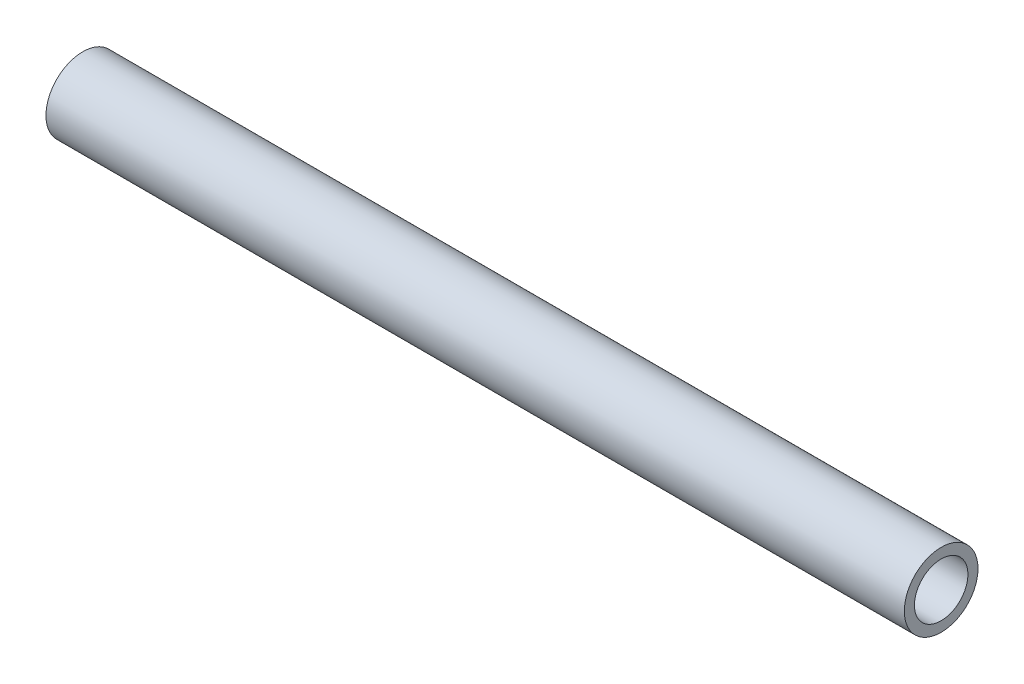
SolidWorks part; units mm, degrees
ref_plane "Front Plane" through (0, 0, 0) normal (0, 0, 1) x (1, 0, 0)
ref_plane "Top Plane" through (0, 0, 0) normal (0, 1, 0) x (1, 0, 0)
ref_plane "Right Plane" through (0, 0, 0) normal (1, 0, 0) x (0, 0, -1)
sketch "Sketch1" plane through (0, 0, 0) normal (1, 0, 0) x (0, 0, -1)
  circle A0 centre (0, 0) radius 13.15
  circle A1 centre (0, 0) radius 9.55
  dimension "D1" = 26.3
  dimension "D2" = 19.1
extrude "Boss-Extrude1" add sketch "Sketch1" along normal blind 306.4
